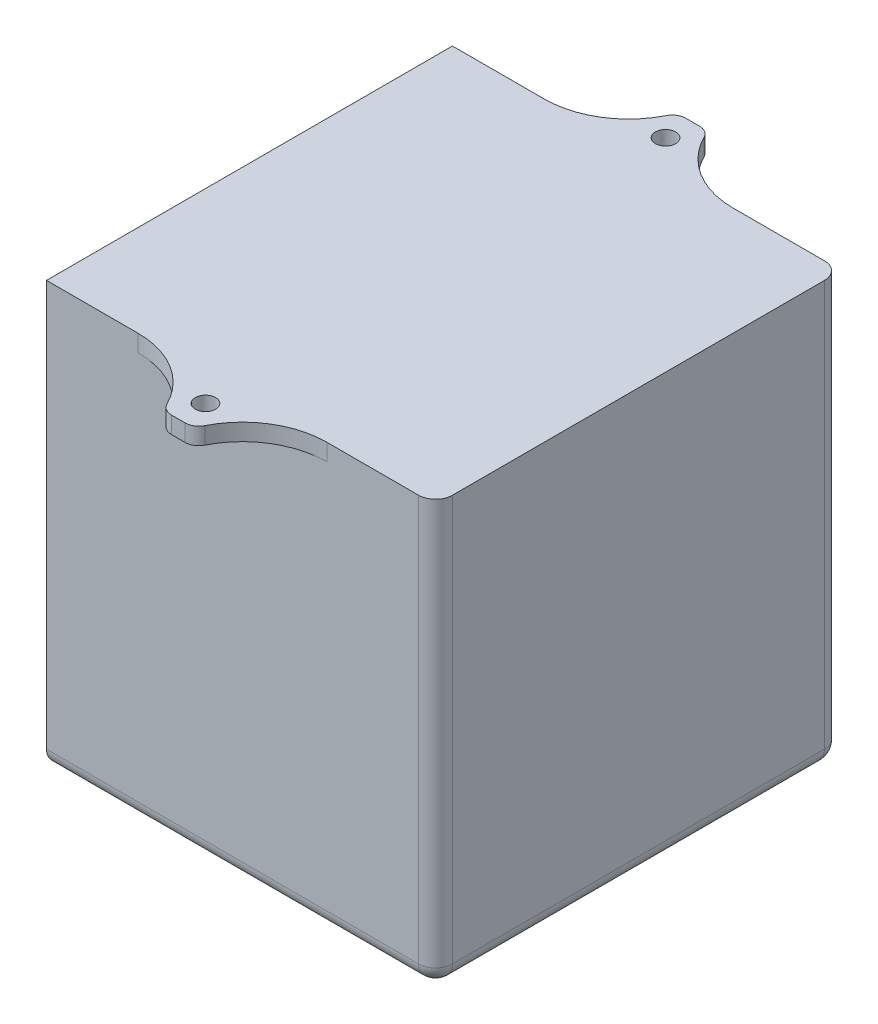
SolidWorks part; units mm, degrees
ref_plane "Front Plane" through (0, 0, 0) normal (0, 0, 1) x (1, 0, 0)
ref_plane "Top Plane" through (0, 0, 0) normal (0, 1, 0) x (1, 0, 0)
ref_plane "Right Plane" through (0, 0, 0) normal (1, 0, 0) x (0, 0, -1)
sketch "Sketch1" plane through (0, 0, 0) normal (0, 1, 0) x (1, 0, 0)
  line L2 (0, 0) -> (60, 0)
  line L3 (0, 0) -> (0, 60)
  line L4 (0, 60) -> (60, 60)
  line L5 (60, 0) -> (60, 60)
  dimension "D1" = 60
  dimension "D2" = 60
extrude "Boss-Extrude1" add sketch "Sketch1" along normal blind 60
shell "Shell1" thickness 2.5 removed face at (30, 0, -30)
sketch "Sketch5" plane through (0, 60, 0) normal (0, 1, 0) x (1, 0, 0)
  line L0 (0, 30) -> (60, 30) construction
  line L1 (0, 60) -> (0, 0) construction
  line L2 (60, 0) -> (60, 60) construction
  line L3 (60, 60) -> (0, 60) construction
  line L4 (30, 64) -> (30, 60) construction
  line L5 (27, 60) -> (27, 66)
  line L6 (29, 68) -> (31, 68)
  line L7 (33, 66) -> (33, 60)
  line L8 (33, 60) -> (27, 60)
  line L9 (30, -4) -> (30, 0) construction
  line L10 (33, 0) -> (27, 0)
  line L11 (33, -6) -> (33, 0)
  line L12 (29, -8) -> (31, -8)
  line L13 (27, 0) -> (27, -6)
  circle A0 centre (30, 64) radius 1.5
  arc A1 (31, 68) -> (33, 66) centre (31, 66) cw
  arc A2 (27, 66) -> (29, 68) centre (29, 66) cw
  arc A3 (27, -6) -> (29, -8) centre (29, -6) ccw
  arc A4 (31, -8) -> (33, -6) centre (31, -6) ccw
  circle A5 centre (30, -4) radius 1.5
  dimension "D1" = 3
  dimension "D6" = 2
  dimension "D2" = 4
  dimension "D3" = 3
  dimension "D4" = 3
  dimension "D5" = 4
extrude "Boss-Extrude3" add sketch "Sketch5" against normal blind 2.5
sketch "Sketch6" plane through (0, 0, 0) normal (0, -1, 0) x (1, 0, 0)
  line L8 (0, 0) -> (0, -60)
  line L9 (0, -60) -> (60, -60)
  line L10 (60, -60) -> (60, 0)
  line L11 (60, 0) -> (0, 0)
  line L12 (0, 0) -> (0, -60)
  line L13 (0, -60) -> (60, -60)
  line L14 (60, -60) -> (60, 0)
  line L15 (60, 0) -> (0, 0)
  dimension "D1" = 0
extrude "Boss-Extrude4" add sketch "Sketch6" along normal blind 2.5
sketch "Sketch7" plane through (0, 0, 0) normal (-1, 0, 0) x (0, 0, 1)
  line L8 (-60, 60) -> (-60, -2.5)
  line L9 (-60, -2.5) -> (0, -2.5)
  line L10 (0, -2.5) -> (0, 60)
  line L11 (0, 60) -> (-60, 60)
  line L12 (-60, 60) -> (-60, -2.5)
  line L13 (-60, -2.5) -> (0, -2.5)
  line L14 (0, -2.5) -> (0, 60)
  line L15 (0, 60) -> (-60, 60)
  dimension "D1" = 0
extrude "Cut-Extrude1" cut sketch "Sketch7" against normal blind 2.5
fillet "Fillet4" radius 2.5 5 edges at (60, 28.75, -60) (60, -2.5, -30) (60, 28.75, 0) (31.25, -2.5, 0) (31.25, -2.5, -60)
fillet "Fillet5" radius 12.5 4 edges at (27, 58.75, 0) (33, 58.75, 0) (33, 58.75, -60) (27, 58.75, -60)
fillet "Fillet6" radius 2.5 8 edges at (57.5, 28.75, -57.5) (57.5, 57.5, -30) (57.5, 28.75, -2.5) (57.5, 0, -30) (30, 0, -2.5) (30, 57.5, -2.5) (30, 57.5, -57.5) (30, 0, -57.5)
